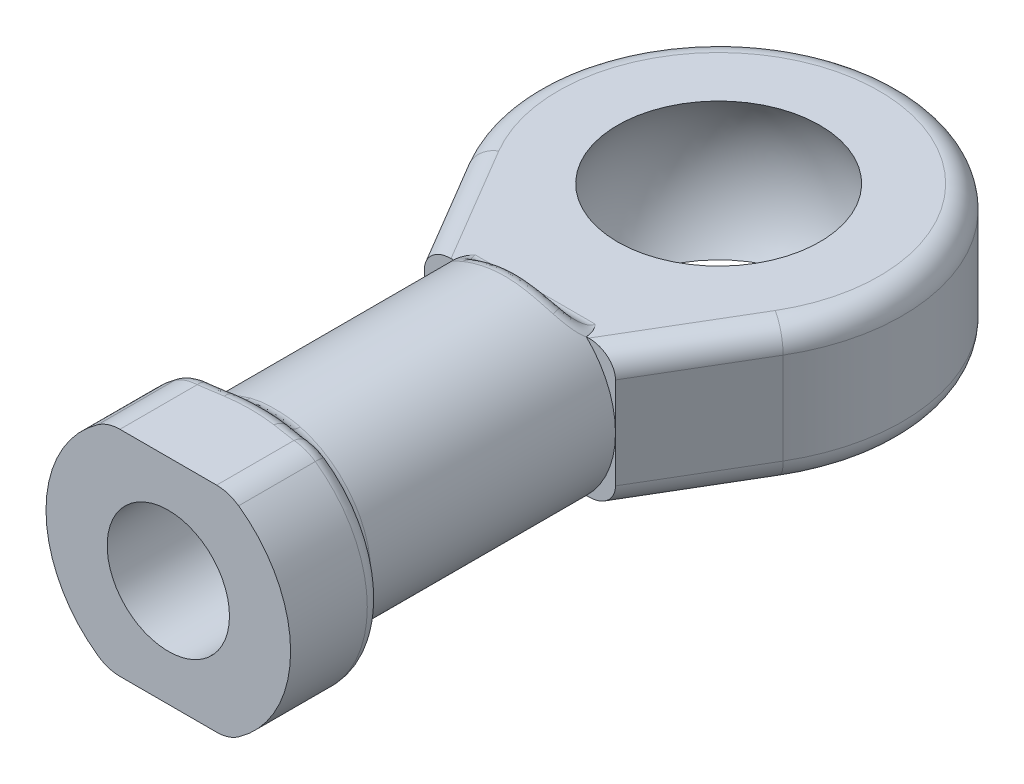
SolidWorks part; units mm, degrees
ref_plane "Front Plane" through (0, 0, 0) normal (0, 0, 1) x (1, 0, 0)
ref_plane "Top Plane" through (0, 0, 0) normal (0, 1, 0) x (1, 0, 0)
ref_plane "Right Plane" through (0, 0, 0) normal (1, 0, 0) x (0, 0, -1)
sketch "Sketch1" plane through (0, 0, 0) normal (0, 1, 0) x (1, 0, 0)
  circle A0 centre (0, 0) radius 12
  dimension "D1" = 24
extrude "Boss-Extrude1" add sketch "Sketch1" along normal blind 9
ref_plane "Plane1" through (0, 4.5, 0) normal (0, 1, 0) x (1, 0, 0)
sketch "Sketch2" plane through (0, 4.5, 0) normal (0, 1, 0) x (1, 0, 0)
  line L0 (-8, 0) -> (8, 0)
  arc A0 (8, 0) -> (-8, 0) centre (0, 0) ccw
  dimension "D1" = 16
revolve "Cut-Revolve1" cut sketch "Sketch2" angle 360 about L0
sketch "Sketch3" plane through (0, 9, 0) normal (0, 1, 0) x (1, 0, 0)
  line L0 (0, -12) -> (0, -36)
  line L3 (-6.25, -36) -> (6.25, -36)
  line L4 (-6.25, -10.2439) -> (-6.25, -36)
  line L7 (6.25, -10.2439) -> (6.25, -36)
  circle A0 centre (0, 0) radius 12 construction
  arc A1 (-6.25, -10.2439) -> (6.25, -10.2439) centre (0, 0) ccw
  circle M3 centre (0, 0) radius 12
extrude "Boss-Extrude2" add sketch "Sketch3" against normal blind 9 contours L7 L0 L3 M3 | L4 L3 L0 M3 region at (3.1616, 9, 23.711) region at (-3.1616, 9, 23.711)
sketch "Sketch4" plane through (0, 9, 0) normal (0, 1, 0) x (1, 0, 0)
  line L1 (6.25, -10.2439) -> (6.25, -36) construction
  line L2 (6.25, -13) -> (-6.25, -13)
  line L3 (-6.25, -10.2439) -> (-6.25, -36) construction
  line L4 (10.3267, -6.1121) -> (6.25, -13)
  line L5 (-10.3267, -6.1121) -> (-6.25, -13)
  line L9 (-6.25, -10.2439) -> (-6.25, -36)
  line L10 (-6.25, -36) -> (6.25, -36)
  line L11 (6.25, -36) -> (6.25, -10.2439)
  line L12 (-6.25, -10.2439) -> (-6.25, -13)
  line L13 (-6.25, -36) -> (6.25, -36)
  line L14 (6.25, -13) -> (6.25, -10.2439)
  arc A0 (6.25, -10.2439) -> (-6.25, -10.2439) centre (0, 0) ccw construction
  arc A1 (-10.3267, -6.1121) -> (-6.25, -10.2439) centre (0, 0) ccw
  arc A2 (6.25, -10.2439) -> (-6.25, -10.2439) centre (0, 0) ccw
  arc A3 (6.25, -10.2439) -> (10.3267, -6.1121) centre (0, 0) ccw
  arc M7 (6.25, -10.2439) -> (-6.25, -10.2439) centre (0, 0) ccw
  line M8 (-6.25, -10.2439) -> (-6.25, -36)
  line M10 (6.25, -36) -> (6.25, -10.2439)
  dimension "D2" = 0
extrude "Boss-Extrude3" add sketch "Sketch4" against normal blind 9 contours L4 M7 M10 | L5 M7 M8 region at (7.3539, 9, 10.2774) region at (-7.3539, 9, 10.2774)
sketch "Sketch5" plane through (0, 0, 36) normal (0, 0, 1) x (1, 0, 0)
  line L0 (0, 9) -> (0, 0)
  line L1 (-6.25, 9) -> (6.25, 9) construction
  line L6 (6.25, 9) -> (-6.25, 9)
  line L7 (-6.25, 9) -> (-6.25, 0)
  line L8 (-6.25, 0) -> (6.25, 0)
  line L9 (6.25, 0) -> (6.25, 9)
  line L10 (6.25, 9) -> (-6.25, 9)
  line L11 (-6.25, 9) -> (-6.25, 0)
  line L12 (-6.25, 0) -> (6.25, 0)
  line L13 (6.25, 0) -> (6.25, 9)
  circle A0 centre (0, 4.5) radius 6.25
  line M1 (6.25, 9) -> (-6.25, 9)
  line M2 (-6.25, 9) -> (-6.25, 0)
  line M3 (-6.25, 0) -> (6.25, 0)
  line M4 (6.25, 0) -> (6.25, 9)
  dimension "D1" = 0
extrude "Cut-Extrude1" cut sketch "Sketch5" against normal blind 23 contours A0 L13 M1 | A0 L10 M2 | A0 L11 M3 | A0 L12 M4 region at (5.6952, 7.9123, 36) region at (-5.6952, 7.9123, 36) region at (-5.6952, 1.0877, 36) region at (5.6952, 1.0877, 36)
sketch "Sketch6" plane through (0, 0, 36) normal (0, 0, 1) x (1, 0, 0)
  circle A0 centre (0, 4.5) radius 6.25
extrude "Boss-Extrude4" add sketch "Sketch6" against normal blind 23
sketch "Sketch7" plane through (0, 0, 36) normal (0, 0, 1) x (1, 0, 0)
  circle A0 centre (0, 4.5) radius 8
  dimension "D1" = 16
extrude "Boss-Extrude6" add sketch "Sketch7" against normal blind 6
sketch "Sketch8" plane through (0, 0, 36) normal (0, 0, 1) x (1, 0, 0)
  line L0 (8, 4.5) -> (-8, 4.5)
  line L1 (0, 4.5) -> (0, 11.5)
  line L2 (0, 4.5) -> (0, -2.5)
  line L3 (0, -2.5) -> (8, -2.5)
  line L4 (8, -2.5) -> (-6.1281, -2.5)
  line L5 (0, 11.5) -> (7.3725, 11.5)
  line L6 (7.3725, 11.5) -> (-8, 11.5)
  circle A0 centre (0, 4.5) radius 8 construction
  circle A2 centre (0, 4.5) radius 8
  circle A3 centre (0, 4.5) radius 8
  circle M4 centre (0, 4.5) radius 8
  dimension "D1" = 7
  dimension "D2" = 7
  dimension "D3" = 0
extrude "Cut-Extrude3" cut sketch "Sketch8" against normal blind 6 and the other way through all contours L6 L5 M4 | L3 L4 M4 region at (0, 11.9022, 36) region at (0, -2.9022, 36)
fillet "Fillet1" radius 2.5 4 edges at (3.873, -2.5, 33) (-3.873, -2.5, 33) (3.873, 11.5, 33) (-3.873, 11.5, 33)
fillet "Fillet2" radius 1 2 edges at (0, 0, 13) (0, 9, 13)
fillet "Fillet3" radius 1 6 edges at (4.2086, 9.1206, 12.4761) (-3.9892, 9.3113, 12.7251) (-4.2086, -0.1206, 12.4761) (3.9892, -0.3113, 12.7251) (0, 10.75, 13) (0, -1.75, 13)
fillet "Fillet4" radius 1 1 edges at (6.25, 4.5, 30)
fillet "Fillet5" radius 1 10 edges at (-3.9161, 11.3837, 30) (-2.5249, 11.5, 30) (0, 11.5, 30) (2.5249, 11.5, 30) (3.9161, 11.3837, 30) (8, 4.5, 30) (2.5249, -2.5, 30) (0, -2.5, 30) (-2.5249, -2.5, 30) (-8, 4.5, 30)
sketch "Sketch9" plane through (0, 0, 36) normal (0, 0, 1) x (1, 0, 0)
  circle A0 centre (0, 4.5) radius 4
  dimension "D1" = 8
extrude "Cut-Extrude4" cut sketch "Sketch9" against normal blind 23
fillet "Fillet6" radius 1.5 6 edges at (8.2884, 0, 9.5561) (-8.2884, 0, 9.5561) (8.2884, 9, 9.5561) (-8.2884, 9, 9.5561) (0, 0, -12) (0, 9, -12)
